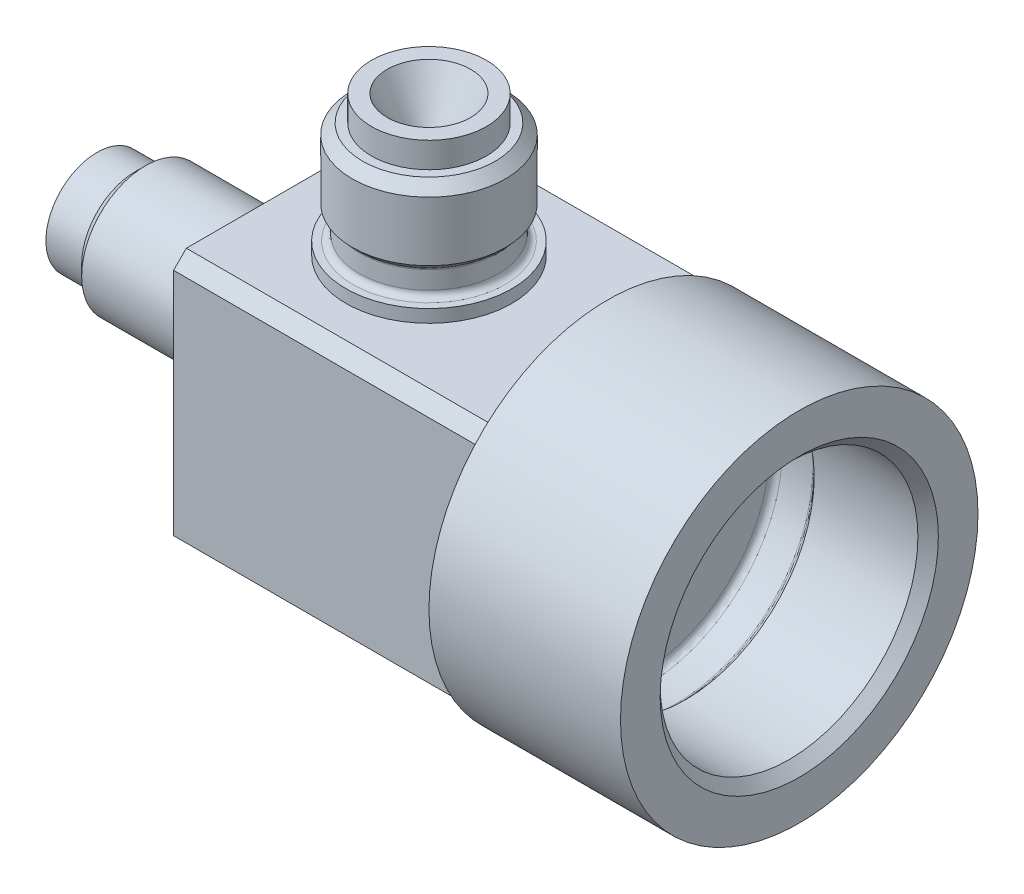
SolidWorks part; units mm, degrees
ref_plane "Спереди" through (0, 0, 0) normal (0, 0, 1) x (1, 0, 0)
ref_plane "Сверху" through (0, 0, 0) normal (0, 1, 0) x (1, 0, 0)
ref_plane "Справа" through (0, 0, 0) normal (1, 0, 0) x (0, 0, -1)
sketch "Эскиз1" plane through (0, 0, 0) normal (0, 0, 1) x (1, 0, 0)
  line L0 (0, 0) -> (-105.287, 0) construction
  line L1 (0, 20.188) -> (0, 28)
  line L2 (0, 28) -> (-30, 28)
  line L3 (0, 20.188) -> (-17.838, 20.188)
  line L4 (-17.838, 20.188) -> (-19, 21.35)
  line L5 (-19, 21.35) -> (-25, 21.35)
  line L6 (-25, 21.35) -> (-25, 12.5)
  line L7 (-25, 12.5) -> (-49, 12.5)
  line L8 (-49, 12.5) -> (-49, 9)
  line L9 (-49, 9) -> (-66, 9)
  line L10 (-66, 9) -> (-66, 5)
  line L11 (-66, 5) -> (-63, 5)
  line L12 (-63, 5) -> (-63, 2.5)
  line L13 (-63, 2.5) -> (-103, 2.5)
  line L14 (-103, 2.5) -> (-110, 6.5415)
  line L15 (-110, 6.5415) -> (-110, 8)
  line L16 (-110, 8) -> (-104, 8)
  line L17 (-104, 8) -> (-104, 10)
  line L18 (-104, 10) -> (-86.1, 10)
  line L19 (-86.1, 10) -> (-85, 8.9)
  line L20 (-85, 8.9) -> (-81, 8.9)
  line L21 (-81, 8.9) -> (-81, 11)
  line L22 (-78, 20) -> (-30, 20)
  line L23 (-30, 20) -> (-30, 28)
  line L24 (-81, 11) -> (-78, 11)
  line L25 (-78, 11) -> (-78, 20)
  dimension "D1" = 40.376
  dimension "D2" = 45
  dimension "D3" = 42.7
  dimension "D4" = 56
  dimension "D5" = 25
  dimension "D6" = 30
  dimension "D7" = 90
  dimension "D8" = 25
  dimension "D9" = 40
  dimension "D10" = 18
  dimension "D11" = 10
  dimension "D12" = 5
  dimension "D13" = 30
  dimension "D14" = 16
  dimension "D15" = 20
  dimension "D16" = 17.8
  dimension "D17" = 22
  dimension "D18" = 32
  dimension "D19" = 29
  dimension "D20" = 7
  dimension "D21" = 6
  dimension "D22" = 4
  dimension "D23" = 45
  dimension "D24" = 3
  dimension "D25" = 63
  dimension "D26" = 49
  dimension "D27" = 110
  dimension "D28" = 6
revolve "Повернуть1" add sketch "Эскиз1" angle 360 about L0
cosmetic thread "Условное изображение резьбы1" parameters "D2"=42
cosmetic thread "Условное изображение резьбы3" parameters "D2"=18.376
sketch "Эскиз2" plane through (-78, 0, 0) normal (-1, 0, 0) x (0, 0, 1)
  line L1 (-20, -20) -> (20, -20)
  line L2 (-20, -20) -> (-20, 20)
  line L3 (-20, 20) -> (20, 20)
  line L4 (20, -20) -> (20, 20)
  line L5 (-20, -20) -> (20, 20) construction
  line L6 (-20, 20) -> (20, -20) construction
  circle A0 centre (0, 0) radius 20 construction
  circle A1 centre (0, 0) radius 20
  point P0 (0, 0)
  circle M4 centre (0, 0) radius 20
  dimension "D1" = 40
extrude "Бобышка-Вытянуть2" add sketch "Эскиз2" against normal up to surface (48 mm away) contours L4 L3 M4 | L3 L2 M4 | L2 L1 M4 | L1 L4 M4 region at (-78, -15.5326, -15.5326) region at (-78, -15.5326, 15.5326) region at (-78, 15.5326, -15.5326) region at (-78, 15.5326, 15.5326) up to face at (-30, 0, -20)
sketch "Эскиз4" plane through (0, 0, 0) normal (0, 0, 1) x (1, 0, 0)
  line L0 (0, 0) -> (-132.4084, 0) construction
  line L1 (-58, 0) -> (-58, 50.6848) construction
  line L2 (-45, 20) -> (-45, 22)
  line L3 (-30, 20) -> (-78, 20) construction
  line L4 (-45, 22) -> (-47.1, 22)
  line L5 (-47.1, 22) -> (-47.1, 26)
  line L6 (-47.1, 26) -> (-46, 27.1)
  line L7 (-46, 27.1) -> (-46, 38)
  line L8 (-58, 35) -> (-55.5, 35)
  line L9 (-46, 38) -> (-49, 38)
  line L10 (-49, 38) -> (-49, 42)
  line L11 (-49, 42) -> (-51.4585, 42)
  line L12 (-51.4585, 42) -> (-55.5, 35)
  line L13 (0, -20.188) -> (0, 20.188) construction
  line L14 (-58, 35) -> (-58, 20)
  line L15 (-58, 20) -> (-45, 20)
  point P14 (-50.2293, 42)
  dimension "D1" = 30
  dimension "D2" = 18
  dimension "D3" = 26
  dimension "D4" = 58
  dimension "D5" = 21.8
  dimension "D6" = 4
  dimension "D7" = 42
  dimension "D8" = 24
  dimension "D9" = 135
  dimension "D10" = 4
  dimension "D11" = 20
  dimension "D12" = 5
  dimension "D13" = 7
revolve "Повернуть2" add sketch "Эскиз4" angle 360 about L1
cosmetic thread "Условное изображение резьбы2" parameters "D2"=22.376
sketch "Эскиз5" plane through (0, 35, 0) normal (0, 1, 0) x (1, 0, 0)
  circle A1 centre (-58, 0) radius 2.5
  circle A2 centre (-58, 0) radius 2.5
  dimension "D1" = 0
extrude "Вырез-Вытянуть1" cut sketch "Эскиз5" against normal up to surface (26.3542 mm away) up to face at (-49, 0, -9)
chamfer "Фаска1" distance 1.6 angle 45 1 edges at (0, 0, -20.188)
chamfer "Фаска2" distance 1.6 angle 45 1 edges at (-58, 38, -12)
fillet "Скругление1" radius 1 3 edges at (-25, 0, -21.35) (-58, 22, -10.9) (-81, 0, -8.9)
fillet "Скругление2" radius 0.5 3 edges at (-19, 0, -21.35) (-58, 26, -10.9) (-85, 0, -8.9)
chamfer "Фаска3" distance 2 angle 45 4 edges at (-54, 20, -20) (-54, -20, -20) (-54, -20, 20) (-54, 20, 20)
chamfer "Фаска4" distance 1.6 angle 45 1 edges at (-104, 0, -10)
